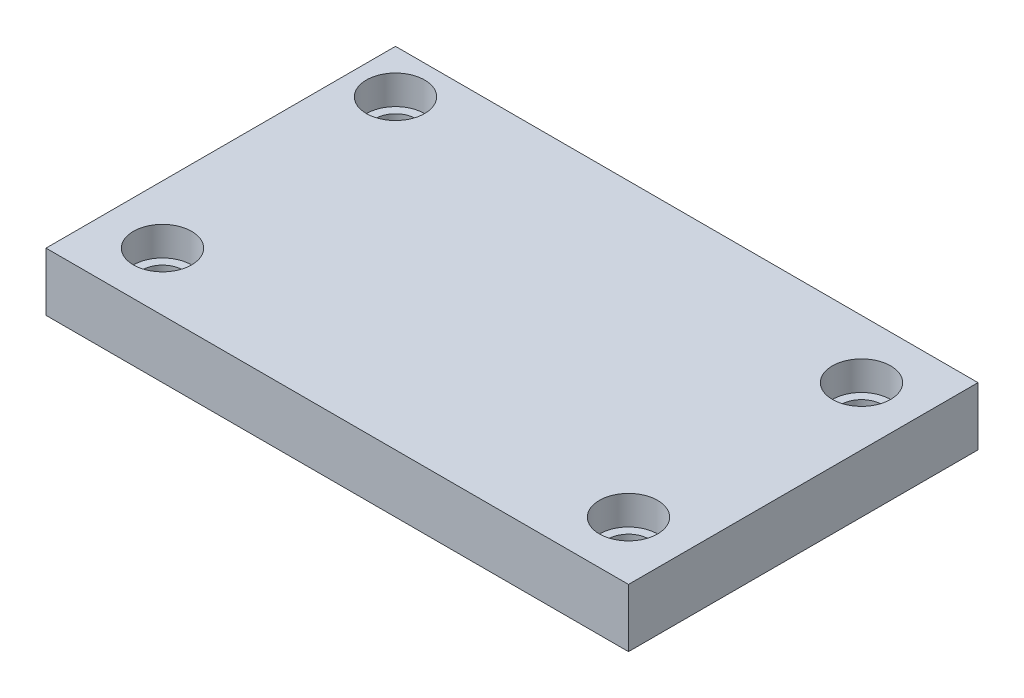
SolidWorks part; units mm, degrees
ref_plane "前视基准面" through (0, 0, 0) normal (0, 0, 1) x (1, 0, 0)
ref_plane "上视基准面" through (0, 0, 0) normal (0, 1, 0) x (1, 0, 0)
ref_plane "右视基准面" through (0, 0, 0) normal (1, 0, 0) x (0, 0, -1)
other "Configuration Table"
sketch "草图1" plane through (0, 0, 0) normal (0, 1, 0) x (1, 0, 0)
  line L1 (0, 0) -> (20, 0)
  line L2 (0, 0) -> (0, -12)
  line L3 (0, -12) -> (20, -12)
  line L4 (20, 0) -> (20, -12)
  circle A0 centre (2, -10) radius 0.7
  circle A1 centre (1.5, -1.5) radius 0.7
  circle A2 centre (18, -2) radius 0.7
  circle A3 centre (18, -10) radius 0.7
  circle A4 centre (2, -10) radius 1
  circle A5 centre (1.5, -1.5) radius 1
  circle A6 centre (18, -2) radius 1
  circle A7 centre (18, -10) radius 1
  point P17 (0, 0)
  point P18 (0, 0)
  point P19 (0, 0)
  point P20 (0, 0)
  dimension "D3" = 1.4
  dimension "D4" = 2
  dimension "D1" = 12
  dimension "D2" = 20
extrude "凸台-拉伸1" add sketch "草图1" along normal blind 2 contours L1 L4 L3 L2 | A2 | A3 | A1 | A0
extrude "切除-拉伸1" cut sketch "草图1<3>" against normal blind 1 from surface contours A4 | A5 | A6 | A7 starting at face at (1.5, 2, 2.2)
sketch "草图1<3>" plane through (0, 0, 0) normal (0, 1, 0) x (1, 0, 0) same geometry as "草图1"
